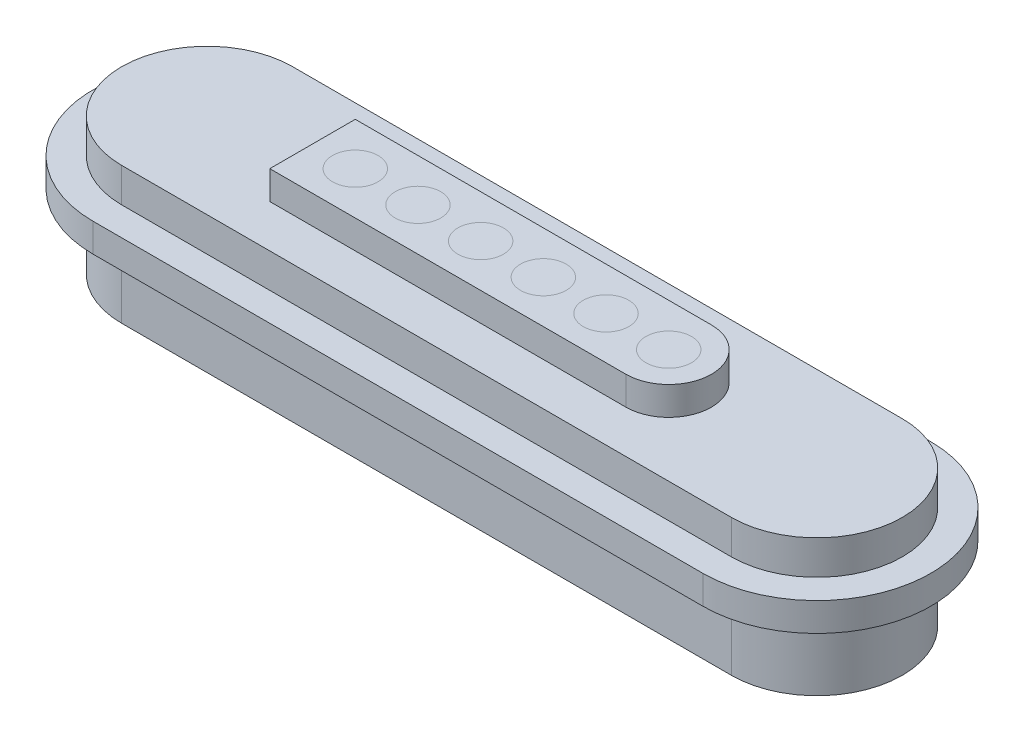
SolidWorks part; units mm, degrees
ref_plane "Front Plane" through (0, 0, 0) normal (0, 0, 1) x (1, 0, 0)
ref_plane "Top Plane" through (0, 0, 0) normal (0, 1, 0) x (1, 0, 0)
ref_plane "Right Plane" through (0, 0, 0) normal (1, 0, 0) x (0, 0, -1)
sketch "Sketch1" plane through (0, 0, 0) normal (0, 1, 0) x (1, 0, 0)
  line L0 (0, 0) -> (21.4, 0) construction
  line L1 (0, 4) -> (21.4, 4)
  line L2 (0, -4) -> (21.4, -4)
  line L3 (0, 0) -> (21.4, 0) construction
  line L4 (0, 3) -> (21.4, 3)
  line L5 (0, -3) -> (21.4, -3)
  line L6 (10.7, 0) -> (10.7, 5.8972) construction
  line L12 (16.9868, -1.3471) -> (3.7, 1.4999) construction
  line L13 (16.9868, 1.3472) -> (3.7, -1.5) construction
  line L14 (16.2, -1.5) -> (3.7, -1.5)
  line L16 (3.7, 1.4999) -> (16.2139, 1.4999)
  line L17 (3.7, -1.5) -> (3.7, 1.4999)
  arc A0 (0, 4) -> (0, -4) centre (0, 0) ccw
  arc A1 (21.4, -4) -> (21.4, 4) centre (21.4, 0) ccw
  arc A2 (0, 3) -> (0, -3) centre (0, 0) ccw
  arc A3 (21.4, -3) -> (21.4, 3) centre (21.4, 0) ccw
  circle A4 centre (11.8, 0) radius 0.8
  circle A5 centre (14, 0) radius 0.8
  circle A6 centre (16.2, 0) radius 0.8
  circle A7 centre (5.2, 0) radius 0.8
  circle A8 centre (7.4, 0) radius 0.8
  circle A9 centre (9.6, 0) radius 0.8
  arc A10 (16.2139, 1.4999) -> (16.2, -1.5) centre (16.2, 0) cw
  point P3 (10.7, 0)
  point P8 (-4, 0)
  point P9 (25.4, 0)
  point P12 (10.7, 0)
  point P37 (17.7, -0.007)
  dimension "D2" = 29.4
  dimension "D4" = 2.2
  dimension "D8" = 1.6
  dimension "D9" = 1.6
  dimension "D10" = 1.6
  dimension "D7" = 14
  dimension "D1" = 8
  dimension "D3" = 6
  dimension "D5" = 2.2
  dimension "D6" = 1.1
extrude "Boss-Extrude1" add sketch "Sketch1" along normal blind 4.8 contours L5 A3 L4 A2 L16 A10 L14 L17 region at (10.7, 0, -2.7195)
extrude "Boss-Extrude2" add sketch "Sketch1<3>" along normal blind 5.8 contours A10 L16 L17 L14 A8 A4 A5 A6 A7 A9 region at (10.4778, 0, 0)
sketch "Sketch1<3>" plane through (0, 0, 0) normal (0, 1, 0) x (1, 0, 0) same geometry as "Sketch1"
extrude "Boss-Extrude3" add sketch "Sketch1<4>" along normal blind 1 from offset 2.6 contours L2 A1 L1 A0 A3 L5 A2 L4 region at (10.7, 0, -3.6953)
sketch "Sketch1<4>" plane through (0, 0, 0) normal (0, 1, 0) x (1, 0, 0) same geometry as "Sketch1"
extrude "Boss-Extrude4" add sketch "Sketch1<5>" along normal blind 5.8 and the other way blind 1.5 separate body contours A7 | A8 | A9 | A4 | A5 | A6 region at (11.8, 0, 0) region at (14, 0, 0) region at (16.2, 0, 0) region at (5.2, 0, 0) region at (7.4, 0, 0) region at (9.6, 0, 0)
sketch "Sketch1<5>" plane through (0, 0, 0) normal (0, 1, 0) x (1, 0, 0) same geometry as "Sketch1"
